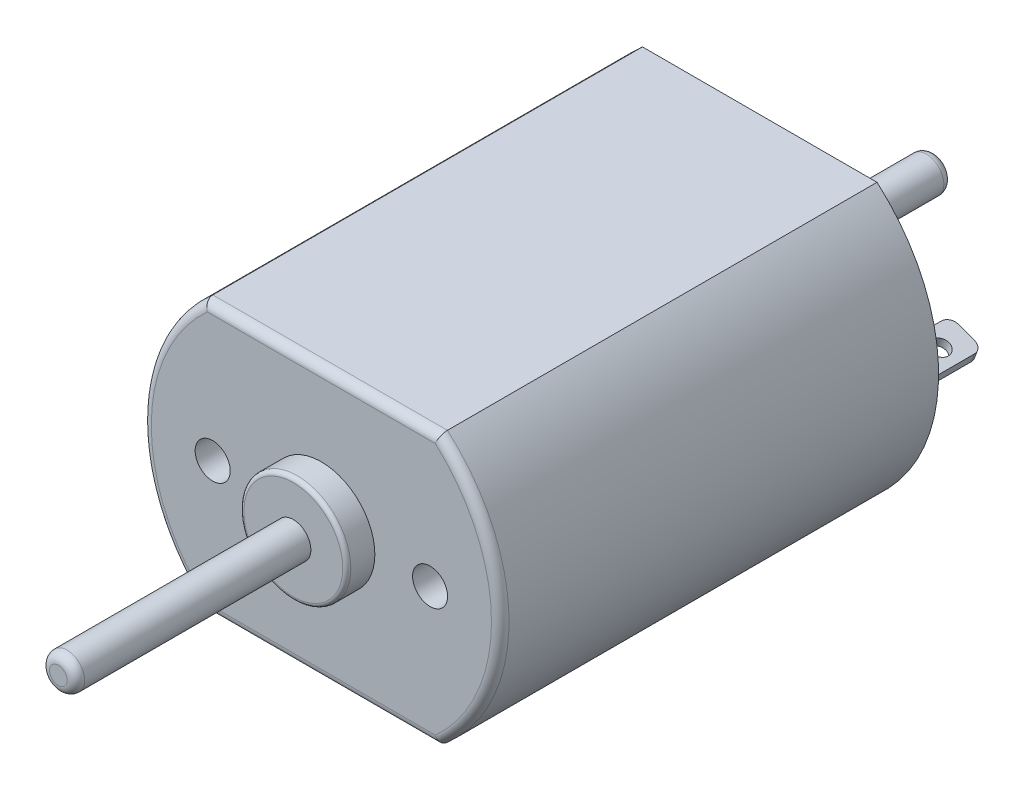
SolidWorks part; units mm, degrees
ref_plane "Front Plane" through (0, 0, 0) normal (0, 0, 1) x (1, 0, 0)
ref_plane "Top Plane" through (0, 0, 0) normal (0, 1, 0) x (1, 0, 0)
ref_plane "Right Plane" through (0, 0, 0) normal (1, 0, 0) x (0, 0, -1)
sketch "Sketch1" plane through (0, 0, 0) normal (0, 0, 1) x (1, 0, 0)
  line L1 (-18.4525, -7.7) -> (18.4525, -7.7)
  line L2 (-18.4525, -7.7) -> (-18.4525, 7.7)
  line L3 (-18.4525, 7.7) -> (18.4525, 7.7)
  line L4 (18.4525, -7.7) -> (18.4525, 7.7)
  line L5 (-18.4525, -7.7) -> (18.4525, 7.7) construction
  line L6 (-18.4525, 7.7) -> (18.4525, -7.7) construction
  circle A0 centre (0, 0) radius 10.2
  dimension "D1" = 20.4
  dimension "D2" = 15.4
extrude "Boss-Extrude1" add sketch "Sketch1" along normal blind 25 contours L3 A0 L1 region at (0, 0, 0)
fillet "Fillet1" radius 0.5 4 edges at (-10.2, 0, 25) (0, -7.7, 25) (10.2, 0, 25) (0, 7.7, 25)
sketch "Sketch2" plane through (0, 0, 25) normal (0, 0, 1) x (1, 0, 0)
  circle A0 centre (0, 0) radius 3.05
  dimension "D1" = 6.1
extrude "Boss-Extrude2" add sketch "Sketch2" along normal blind 1.6
sketch "Sketch3" plane through (0, 0, 26.6) normal (0, 0, 1) x (1, 0, 0)
  circle A0 centre (0, 0) radius 1
  dimension "D1" = 2
extrude "Boss-Extrude3" add sketch "Sketch3" along normal offset from surface (13.4 mm away) 15 up to face at (3.05, 0, 25) offset beyond the face yes
sketch "Sketch4" plane through (0, 0, 0) normal (0, 0, -1) x (-1, 0, 0)
  circle A0 centre (0, 0) radius 3.075
  dimension "D1" = 6.15
extrude "Boss-Extrude4" add sketch "Sketch4" along normal blind 2
fillet "Fillet2" radius 0.23 2 edges at (3.05, 0, 26.6) (-3.075, 0, -2)
sketch "Sketch5" plane through (0, 0, -2) normal (0, 0, -1) x (-1, 0, 0)
  circle A0 centre (0, 0) radius 1
  dimension "D1" = 2
extrude "Boss-Extrude6" add sketch "Sketch5" along normal offset from surface (8 mm away) 10 up to face at (-3.075, 0, 0) offset beyond the face yes
fillet "Fillet3" radius 0.5 2 edges at (1, 0, 40) (1, 0, -10)
sketch "Sketch6" plane through (0, 0, 0) normal (0, 0, -1) x (-1, 0, 0)
  line L0 (0, 0) -> (13.2626, 0) construction
  line L1 (7.0021, 1.7) -> (13.5461, 1.7) construction
  line L2 (7.4166, -1.7) -> (13.0226, -1.7) construction
  line L3 (7.4074, 1.7) -> (13.7175, 4.0384) construction
  line L4 (-7.4074, -1.7) -> (-12.4105, -3.554) construction
  line L6 (-8.2582, -2.2819) -> (-6.3829, -1.5869)
  line L7 (-8.2582, -2.2819) -> (-8.432, -1.8131)
  line L8 (-8.432, -1.8131) -> (-6.5566, -1.1181)
  line L9 (-6.3829, -1.5869) -> (-6.5566, -1.1181)
  line L10 (-8.2582, -2.2819) -> (-6.5566, -1.1181) construction
  line L11 (-8.432, -1.8131) -> (-6.3829, -1.5869) construction
  line L12 (8.432, 1.8131) -> (6.5566, 1.1181)
  line L13 (8.432, 1.8131) -> (8.2582, 2.2819)
  line L14 (8.2582, 2.2819) -> (6.3829, 1.5869)
  line L15 (6.5566, 1.1181) -> (6.3829, 1.5869)
  line L16 (8.432, 1.8131) -> (6.3829, 1.5869) construction
  line L17 (8.2582, 2.2819) -> (6.5566, 1.1181) construction
  circle A0 centre (0, 0) radius 7.6 construction
  circle A1 centre (7.4074, 1.7) radius 1.2
  circle A2 centre (-7.4074, -1.7) radius 1.2
  dimension "D4" = 15.2
  dimension "D6" = 2.4
  dimension "D1" = 1.7
  dimension "D2" = 1.7
  dimension "D3" = 3.4
  dimension "D5" = 20.333
  dimension "D7" = 2
  dimension "D8" = 0.5
extrude "Boss-Extrude7" add sketch "Sketch6" along normal blind 4.3 contours L6 L9 L8 L7 | L15 L12 L13 L14 region at (7.4074, -1.7, 0) region at (-7.4074, 1.7, 0)
extrude "Boss-Extrude8" add sketch "Sketch6<3>" along normal blind 0.3 contours A2 L9 L6 L7 L8 | A1 L12 L15 L14 L13 region at (-6.2414, 1.7, 0) region at (8.5735, -1.7, 0)
sketch "Sketch6<3>" plane through (0, 0, 0) normal (0, 0, -1) x (-1, 0, 0) same geometry as "Sketch6"
fillet "Fillet4" radius 0.5 4 edges at (-8.3451, 2.0475, -4.3) (-6.4697, 1.3525, -4.3) (6.4697, -1.3525, -4.3) (8.3451, -2.0475, -4.3)
sketch "Sketch7" plane through (0.2536, 0.6844, 0) normal (-0.3475, -0.9377, 0) x (0.9377, -0.3475, 0)
  line L0 (7.5366, -4.3) -> (7.5366, 1.7024) construction
  line L1 (8.0366, -4.3) -> (7.0366, -4.3) construction
  line L2 (-7.5366, -4.3) -> (-7.5366, 1.4762) construction
  line L3 (-8.0366, -4.3) -> (-7.0366, -4.3) construction
  line L4 (-7.5366, -2.8) -> (7.5366, -2.8) construction
  circle A0 centre (-7.5366, -2.8) radius 0.5
  circle A1 centre (7.5366, -2.8) radius 0.5
  dimension "D1" = 1
  dimension "D2" = 1.5
extrude "Cut-Extrude1" cut sketch "Sketch7" against normal through all and the other way through all
sketch "Sketch8" plane through (0, 0, 25) normal (0, 0, 1) x (1, 0, 0)
  line L0 (-6.2, 0) -> (6.2, 0) construction
  circle A0 centre (0, 0) radius 6.2 construction
  dimension "D1" = 12.4
hole_wizard "Ø2.0 (2) Diameter Hole1" positions "Sketch9" profile "Sketch10" hole size "Ø2.0" standard "ANSI Metric"
sketch "Sketch9" plane through (0, 0, 25) normal (0, 0, 1) x (1, 0, 0)
  point P0 (-6.2, 0)
  point P3 (6.2, 0)
sketch "Sketch10" plane through (-6.2, 0, 25) normal (1, 0, 0) x (0, -1, 0)
  line L0 (0, 0) -> (0, 2.6009)
  line L1 (0, 2.6009) -> (1, 2)
  line L2 (1, 2) -> (1, 0)
  line L5 (1, 0) -> (0, 0)
  line L10 (0, 2.6009) -> (-1, 2) construction
  line L11 (0, -6.35) -> (0, 107.95) construction
  dimension "Hole Dia." = 2
  dimension "Hole Depth" = 2
  dimension "Drill Angle" = 118
